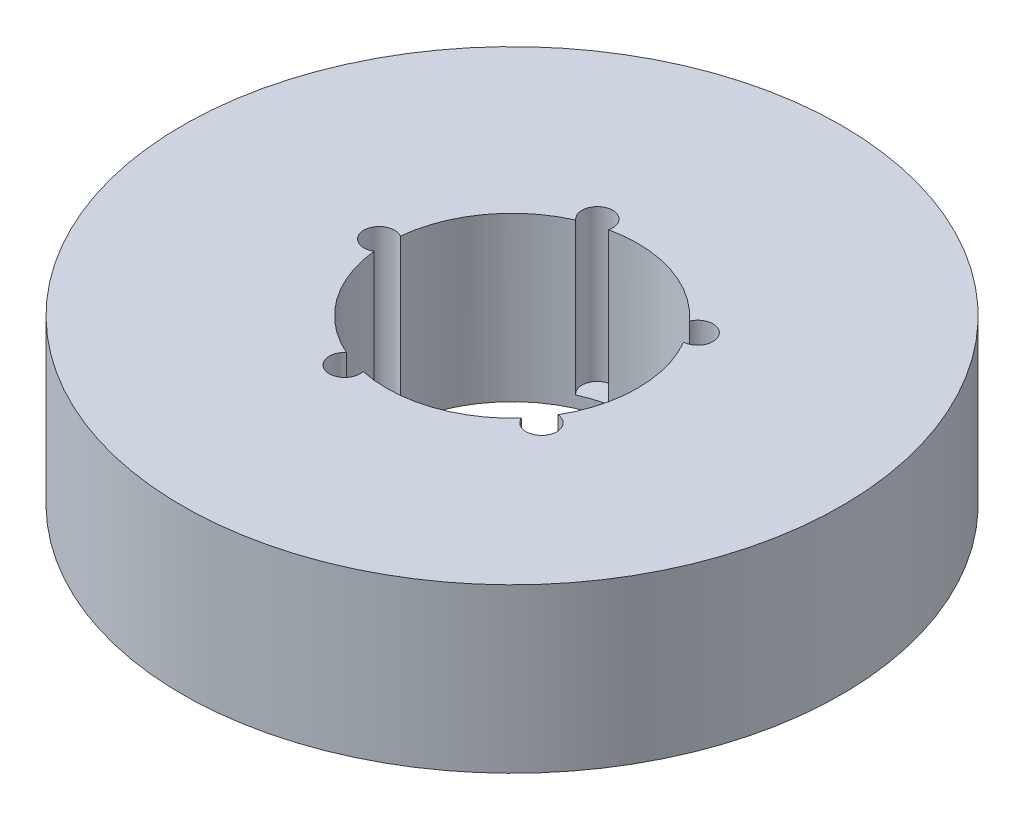
SolidWorks part; units mm, degrees
ref_plane "Front Plane" through (0, 0, 0) normal (0, 0, 1) x (1, 0, 0)
ref_plane "Top Plane" through (0, 0, 0) normal (0, 1, 0) x (1, 0, 0)
ref_plane "Right Plane" through (0, 0, 0) normal (1, 0, 0) x (0, 0, -1)
sketch "Sketch1" plane through (0, 0, 0) normal (0, 1, 0) x (1, 0, 0)
  circle A0 centre (0, 0) radius 52.5
  dimension "FLANGE_OD" = 105
extrude "Boss-Extrude1" add sketch "Sketch1" along normal blind 26
sketch "Sketch2" plane through (0, 0, 0) normal (0, 1, 0) x (1, 0, 0)
  circle A0 centre (0, 0) radius 20
  dimension "BORE_D" = 40
extrude "Cut-Extrude1" cut sketch "Sketch2" along normal through all
sketch "Sketch3" plane through (0, 26, 0) normal (0, 1, 0) x (1, 0, 0)
  circle A0 centre (0, 0) radius 21.1642 construction
  circle A1 centre (-21.1642, 0) radius 2.444
  dimension "BOLT_D" = 4.8881
  dimension "BOLT_PCD" = 42.3284
extrude "Cut-Extrude2" cut sketch "Sketch3" against normal blind 24.1272
pattern_circular "CirPattern1" count 5 over 360 about axis through (0, 0, 0) along (0, 1, 0) of "Cut-Extrude2"
